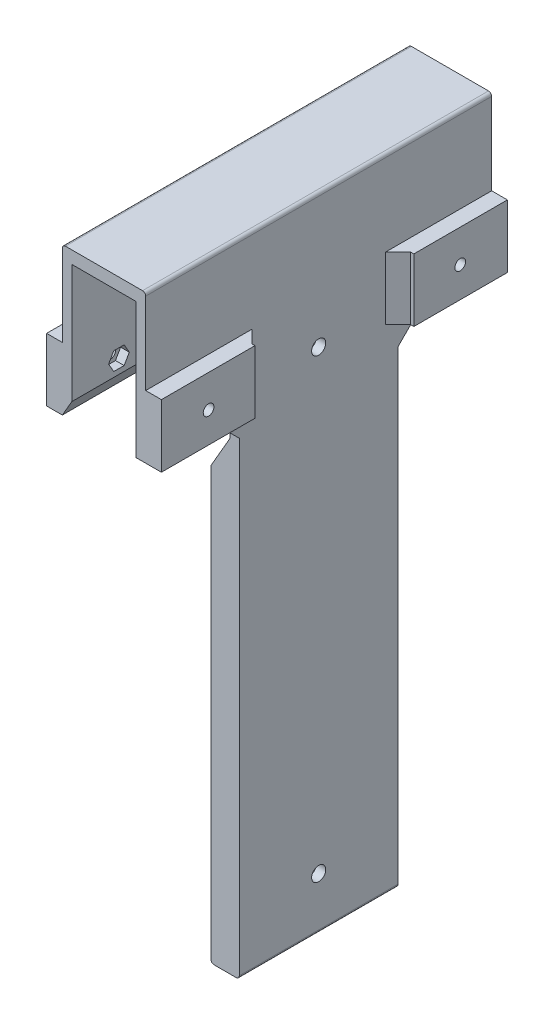
SolidWorks part; units mm, degrees
ref_plane "前视基准面" through (0, 0, 0) normal (0, 0, 1) x (1, 0, 0)
ref_plane "上视基准面" through (0, 0, 0) normal (0, 1, 0) x (1, 0, 0)
ref_plane "右视基准面" through (0, 0, 0) normal (1, 0, 0) x (0, 0, -1)
sketch "草图1" plane through (0, 0, 0) normal (0, 0, 1) x (1, 0, 0)
  line L0 (0, 0) -> (20.5, 0)
  line L1 (20.5, 0) -> (20.5, -196)
  line L2 (20.5, -196) -> (14.5, -196)
  line L3 (14.5, -196) -> (14.5, -200)
  line L4 (14.5, -200) -> (23.5, -200)
  line L5 (23.5, -200) -> (23.5, 4)
  line L6 (23.5, 4) -> (-3, 4)
  line L7 (-3, 4) -> (-3, -43)
  line L8 (-3, -43) -> (0, -43)
  line L9 (0, -43) -> (0, 0)
  point P11 (23.5, -98)
  point P12 (5.8185, -150)
  point P13 (23.5, -150)
  point P14 (20.5, -146.1435)
  dimension "D1" = 3
  dimension "D2" = 3
  dimension "D3" = 4
  dimension "D4" = 20.5
  dimension "D5" = 6
  dimension "D6" = 200
  dimension "D7" = 4
  dimension "D8" = 43
extrude "凸台-拉伸1" add sketch "草图1" along normal blind 110
sketch "草图3" plane through (0, 0, 0) normal (0, 0, -1) x (-1, 0, 0)
  line L0 (-23.5, -200) -> (-23.5, 4) construction
  line L1 (-23.5, -23) -> (-28.5, -23)
  line L2 (-23.5, -23) -> (-23.5, -43)
  line L3 (-23.5, -43) -> (-28.5, -43)
  line L4 (-28.5, -23) -> (-28.5, -43)
  line L5 (3, 4) -> (3, -43) construction
  line L6 (3, -23) -> (8, -23)
  line L7 (3, -23) -> (3, -43)
  line L8 (3, -43) -> (8, -43)
  line L9 (8, -23) -> (8, -43)
  line L10 (-20.5, 0) -> (-20.5, -196) construction
  line L11 (0, 0) -> (-20.5, 0) construction
  point P16 (-28.5, -33)
  dimension "D1" = 8
  dimension "D2" = 33
  dimension "D3" = 20
extrude "凸台-拉伸2" add sketch "草图3" against normal up to surface (110 mm away) up to face at (11.1, -87, 110)
sketch "草图2" plane through (23.5, 0, 0) normal (1, 0, 0) x (0, 0, -1)
  line L0 (-55, -38.5) -> (-55, -183.5) construction
  line L1 (-110, 4) -> (0, 4) construction
  circle A0 centre (-55, -38.5) radius 2.25
  circle A1 centre (-55, -183.5) radius 2.25
  point P6 (-55, 4)
  point P7 (-55, -111)
  dimension "D2" = 4.5
  dimension "D1" = 145
  dimension "D3" = 115
  dimension "D4" = 42.5
extrude "切除-拉伸1" cut sketch "草图2" against normal up to next
sketch "草图5" plane through (0, 4, 0) normal (0, 1, 0) x (1, 0, 0)
  line L0 (-8, -110) -> (-8, 0) construction
  line L1 (-8, -80.25) -> (-3, -80.25)
  line L2 (-8, -80.25) -> (-8, -29.75)
  line L3 (-8, -29.75) -> (-3, -29.75)
  line L4 (-3, -80.25) -> (-3, -29.75)
  line L6 (-3, -110) -> (-3, 0) construction
  line L7 (10.25, 0) -> (10.25, -34.2258) construction
  line L8 (23.5, 0) -> (-3, 0) construction
  line L9 (28.5, -29.75) -> (23.5, -29.75)
  line L10 (23.5, -80.25) -> (23.5, -29.75)
  line L11 (28.5, -80.25) -> (23.5, -80.25)
  line L12 (28.5, -80.25) -> (28.5, -29.75)
  point P8 (-8, -55)
  point P9 (-8, -55)
  dimension "D1" = 50.5
extrude "切除-拉伸2" cut sketch "草图5" against normal through all
sketch "草图6" plane through (23.5, 0, 0) normal (1, 0, 0) x (0, 0, -1)
  line L0 (-80.25, -43) -> (-80.25, -23) construction
  line L1 (-110, -200) -> (-80.25, -200)
  line L2 (-110, -200) -> (-110, -43)
  line L3 (-110, -43) -> (-80.25, -43)
  line L4 (-80.25, -200) -> (-80.25, -43)
  line L5 (0, -200) -> (-29.75, -200)
  line L6 (0, -200) -> (0, -43)
  line L7 (0, -43) -> (-29.75, -43)
  line L8 (-29.75, -200) -> (-29.75, -43)
  line L9 (-29.75, -43) -> (-29.75, -23) construction
  point P14 (-110, -43)
extrude "切除-拉伸3" cut sketch "草图6" against normal blind 10
sketch "草图7" plane through (20.5, 0, 0) normal (-1, 0, 0) x (0, 0, 1)
  line L1 (29.75, -196) -> (32.75, -196)
  line L2 (29.75, -196) -> (29.75, -51)
  line L3 (29.75, -51) -> (32.75, -51)
  line L4 (32.75, -196) -> (32.75, -51)
  line L5 (55, 4) -> (55, -36.0577) construction
  line L6 (110, 4) -> (0, 4) construction
  line L7 (80.25, -51) -> (77.25, -51)
  line L8 (77.25, -196) -> (77.25, -51)
  line L9 (80.25, -196) -> (77.25, -196)
  line L10 (80.25, -196) -> (80.25, -51)
  line L11 (80.25, -43) -> (29.75, -43) construction
  point P11 (0, 0)
  dimension "D1" = 3
  dimension "D2" = 8
extrude "凸台-拉伸3" add sketch "草图7" along normal up to surface (6 mm away) up to face at (14.5, -198, 55)
fillet "圆角1" radius 1 7 edges at (14.5, -196, 55) (14.5, -200, 55) (20.5, -196, 55) (23.5, -200, 55) (-3, -43, 55) (23.5, 4, 55) (-3, 4, 55)
chamfer "倒角1" distance 8 angle 45 2 edges at (22, -43, 80.25) (22, -43, 29.75)
chamfer "倒角2" distance 4 angle 45 6 edges at (-2.7071, -42.7071, 29.75) (-3, -32.5, 29.75) (-2.7071, -42.7071, 80.25) (-3, -32.5, 80.25) (23.5, -33, 29.75) (23.5, -33, 80.25)
sketch "草图8" plane through (-8, 0, 0) normal (-1, 0, 0) x (0, 0, 1)
  line L0 (15, -33.335) -> (95, -33.335) construction
  line L1 (110, 3) -> (0, 3) construction
  circle A0 centre (15, -33.335) radius 1.7
  circle A1 centre (95, -33.335) radius 1.7
  point P4 (55, -33.335)
  point P7 (55, 3)
  dimension "D2" = 3.4
  dimension "D1" = 80
extrude "切除-拉伸4" cut sketch "草图8" against normal through all
ref_plane "基准面1" through (10.25, 0, 0) normal (1, 0, 0) x (0, 0, -1)
sketch "草图9" plane through (10.25, 0, 0) normal (1, 0, 0) x (0, 0, -1)
  line L1 (-93.3546, -30.485) -> (-96.6454, -30.485)
  line L2 (-96.6454, -30.485) -> (-98.2909, -33.335)
  line L3 (-98.2909, -33.335) -> (-96.6454, -36.185)
  line L4 (-96.6454, -36.185) -> (-93.3546, -36.185)
  line L5 (-93.3546, -36.185) -> (-91.7091, -33.335)
  line L6 (-91.7091, -33.335) -> (-93.3546, -30.485)
  line L7 (-13.3546, -30.485) -> (-16.6454, -30.485)
  line L8 (-16.6454, -30.485) -> (-18.2909, -33.335)
  line L9 (-18.2909, -33.335) -> (-16.6454, -36.185)
  line L10 (-16.6454, -36.185) -> (-13.3546, -36.185)
  line L11 (-13.3546, -36.185) -> (-11.7091, -33.335)
  line L12 (-11.7091, -33.335) -> (-13.3546, -30.485)
  circle A0 centre (-95, -33.335) radius 2.85 construction
  circle A1 centre (-15, -33.335) radius 2.85 construction
  dimension "D1" = 5.7
extrude "切除-拉伸5" cut sketch "草图9" against normal blind 13 and the other way blind 13
chamfer "倒角3" distance 12 angle 30 2 edges at (14.5, -51, 78.75) (14.5, -51, 31.25) first distance on face at (14.5, -124.5, 55)
chamfer "倒角4" distance 3 angle 60 1 edges at (0, -43, 55) first distance on face at (-4.8708, -43, 55.1478)
